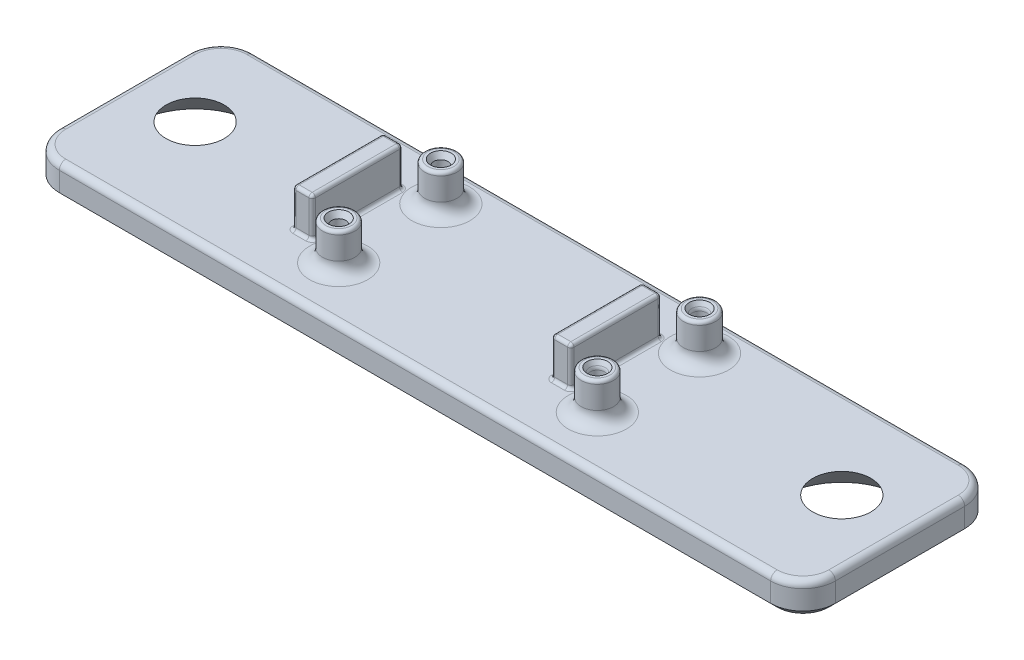
SolidWorks part; units mm, degrees
ref_plane "Спереди" through (0, 0, 0) normal (0, 0, 1) x (1, 0, 0)
ref_plane "Сверху" through (0, 0, 0) normal (0, 1, 0) x (1, 0, 0)
ref_plane "Справа" through (0, 0, 0) normal (1, 0, 0) x (0, 0, -1)
sketch "Эскиз1" plane through (0, 0, 0) normal (0, 1, 0) x (1, 0, 0)
  line L0 (50, 1) -> (-69.2125, 1) construction
  line L1 (-60, -15) -> (60, -15)
  line L2 (-60, -15) -> (-60, 15)
  line L3 (-60, 15) -> (60, 15)
  line L4 (60, -15) -> (60, 15)
  line L5 (0, 15) -> (0, -15) construction
  line L6 (-60, 0) -> (60, 0) construction
  circle A0 centre (-50, 1) radius 4.5
  circle A1 centre (50, 1) radius 4.5
  point P0 (0, 0)
  dimension "D3" = 100
  dimension "D4" = 9
  dimension "D6" = 16
  dimension "D1" = 120
  dimension "D2" = 30
  dimension "D5" = 10
extrude "Бобышка-Вытянуть1" add sketch "Эскиз1" along normal blind 5
fillet "Скругление1" radius 5 4 edges at (-60, 2.5, -15) (-60, 2.5, 15) (60, 2.5, -15) (60, 2.5, 15)
sketch "Эскиз2" plane through (0, 5, 0) normal (0, 1, 0) x (1, 0, 0)
  line L0 (20, 9) -> (20, -21.0588) construction
  line L1 (37.0312, 9) -> (-50.4859, 9) construction
  line L2 (55, 15) -> (-55, 15) construction
  line L3 (0, 24.378) -> (0, -24.8256) construction
  line L4 (15, -5.9) -> (15, 8.1)
  line L5 (15, -5.9) -> (12, -5.9)
  line L6 (12, -5.9) -> (12, 8.1)
  line L7 (15, 8.1) -> (12, 8.1)
  line L8 (12, 1.1) -> (15, 1.1) construction
  line L9 (13.5, -5.9) -> (13.5, 8.1) construction
  line L22 (-25, -5.9) -> (-25, 8.1)
  line L23 (-25, -5.9) -> (-28, -5.9)
  line L24 (-28, -5.9) -> (-28, 8.1)
  line L25 (-25, 8.1) -> (-28, 8.1)
  line L26 (-28, 1.1) -> (-25, 1.1) construction
  line L27 (-26.5, -5.9) -> (-26.5, 8.1) construction
  circle A0 centre (20, 9) radius 2.5
  circle A1 centre (20, -6.8) radius 2.5
  circle A2 centre (20, -6.8) radius 1.1
  circle A3 centre (20, 9) radius 1.1
  circle A12 centre (-20, 9) radius 2.5
  circle A13 centre (-20, -6.8) radius 2.5
  circle A14 centre (-20, -6.8) radius 1.1
  circle A15 centre (-20, 9) radius 1.1
  point P12 (13.5, 1.1)
  point P25 (-26.5, 1.1)
  dimension "D1" = 5
  dimension "D2" = 6
  dimension "D3" = 2.2
  dimension "D4" = 15.8
  dimension "D5" = 8
  dimension "D6" = 14
  dimension "D7" = 0.9
  dimension "D8" = 20
  dimension "D9" = 3
  dimension "D10" = 2
extrude "Бобышка-Вытянуть2" add sketch "Эскиз2" along normal blind 6
sketch "Эскиз3" plane through (0, 11, 0) normal (0, 1, 0) x (1, 0, 0)
  circle A0 centre (20, -6.8) radius 1.1
  circle A1 centre (20, 9) radius 1.1
  circle A2 centre (20, 9) radius 1.1 construction
  circle A3 centre (20, -6.8) radius 1.1 construction
extrude "Вырез-Вытянуть1" cut sketch "Эскиз3" against normal blind 8
fillet "Скругление2" radius 2 4 edges at (20, 5, -11.5) (20, 5, 4.3) (-20, 5, -11.5) (-20, 5, 4.3)
fillet "Скругление3" radius 0.5 28 edges at (12, 5, -1.1) (15, 5, -1.1) (15, 8, -8.1) (12, 8, -8.1) (13.5, 5, -8.1) (12, 8, 5.9) (15, 8, 5.9) (13.5, 5, 5.9) (15, 11, -1.1) (13.5, 11, 5.9) (12, 11, -1.1) (13.5, 11, -8.1) (-28, 5, -1.1) (-25, 5, -1.1) (-25, 8, -8.1) (-28, 8, -8.1) (-26.5, 5, -8.1) (-28, 8, 5.9) (-25, 8, 5.9) (-26.5, 5, 5.9) (-25, 11, -1.1) (-26.5, 11, 5.9) (-28, 11, -1.1) (-26.5, 11, -8.1) (-20, 11, 4.3) (-20, 11, -6.5) (20, 11, -6.5) (20, 11, 4.3)
fillet "Скругление4" radius 1 8 edges at (-58.5355, 5, -13.5355) (0, 5, -15) (58.5355, 5, -13.5355) (60, 5, 0) (58.5355, 5, 13.5355) (0, 5, 15) (-58.5355, 5, 13.5355) (-60, 5, 0)
chamfer "Фаска1" distance 5 angle 45 2 edges at (50, 0, -5.5) (-50, 0, 3.5)
chamfer "Фаска2" distance 1 angle 45 8 edges at (0, 0, 15) (58.5355, 0, 13.5355) (-58.5355, 0, 13.5355) (60, 0, 0) (-60, 0, 0) (58.5355, 0, -13.5355) (-58.5355, 0, -13.5355) (0, 0, -15)
sketch "Эскиз4" plane through (0, 11, 0) normal (0, 1, 0) x (1, 0, 0)
  line L1 (9.8801, -16.7867) -> (26.379, -16.7867)
  line L2 (9.8801, -16.7867) -> (9.8801, 16.7867)
  line L3 (9.8801, 16.7867) -> (26.379, 16.7867)
  line L4 (26.379, -16.7867) -> (26.379, 16.7867)
  line L5 (18.1296, 16.7867) -> (18.1296, -16.7867) construction
  line L6 (9.8801, 0) -> (26.379, 0) construction
  point P0 (18.1296, 0)
extrude "Вырез-Вытянуть-Тонкостенный1" [suppressed] cut sketch "Эскиз4" against normal blind 20 thin thin type one direction wall 100
chamfer "Фаска3" distance 0.5 angle 60 4 edges at (20, 11, 7.9) (20, 11, -10.1) (-20, 11, 7.9) (-20, 11, -10.1) first distance on face at (20, 11, 4.8) first distance on face at (20, 11, -7) first distance on face at (-20, 11, 4.8) first distance on face at (-20, 11, -7)
fillet "Скругление5" radius 1 2 edges at (20, 10.134, 5.7) (20, 10.134, -7.9)
